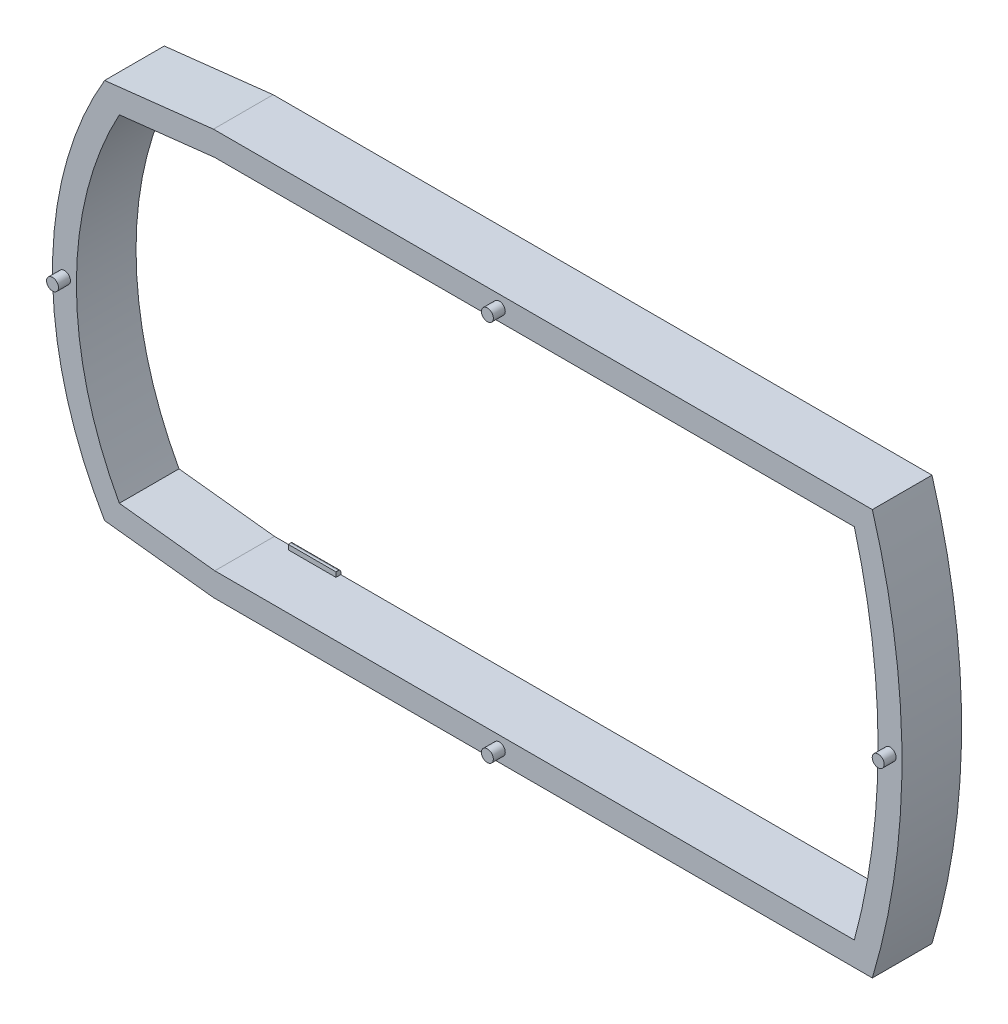
SolidWorks part; units mm, degrees
ref_plane "Plan de face" through (0, 0, 0) normal (0, 0, 1) x (1, 0, 0)
ref_plane "Plan de dessus" through (0, 0, 0) normal (0, 1, 0) x (1, 0, 0)
ref_plane "Plan de droite" through (0, 0, 0) normal (1, 0, 0) x (0, 0, -1)
sketch "Esquisse1" plane through (0, 0, 0) normal (0, 0, 1) x (1, 0, 0)
  line L0 (-192.776, 43.345) -> (-152.776, 47.845)
  line L1 (-152.776, 47.845) -> (115.224, 47.845)
  line L2 (-152.776, 47.845) -> (-152.776, -102.155)
  line L3 (-152.776, -102.155) -> (115.224, -102.155)
  line L4 (115.224, 47.845) -> (115.224, -102.155)
  line L5 (-152.776, 47.845) -> (-192.776, 47.845)
  line L6 (-152.776, 53.8314) -> (-152.776, -102.155)
  line L7 (-152.776, 47.845) -> (-152.776, -102.155)
  line L8 (-152.776, -102.155) -> (-192.776, -102.155)
  line L9 (-192.776, 47.845) -> (-192.776, -102.155)
  line L10 (-152.776, 47.845) -> (-192.776, 47.845)
  line L11 (-152.776, 47.845) -> (-152.776, 43.345)
  line L12 (-152.776, 43.345) -> (-192.776, 43.345)
  line L13 (-192.776, 47.845) -> (-192.776, 43.345)
  line L14 (-152.776, -102.155) -> (-192.776, -102.155)
  line L15 (-152.776, -102.155) -> (-152.776, -97.655)
  line L16 (-152.776, -97.655) -> (-192.776, -97.655)
  line L17 (-192.776, -102.155) -> (-192.776, -97.655)
  line L18 (-192.776, -97.655) -> (-152.776, -102.155)
  line L20 (124.9119, -14.655) -> (121.9119, -14.655)
  line L21 (124.9119, -14.655) -> (124.9119, -39.655)
  line L22 (124.9119, -39.655) -> (121.9119, -39.655)
  line L23 (121.9119, -14.655) -> (121.9119, -39.655)
  line L24 (-144.9874, 47.845) -> (-124.9874, 47.845)
  line L25 (-144.9874, 47.845) -> (-144.9874, 45.845)
  line L26 (-144.9874, 45.845) -> (-124.9874, 45.845)
  line L27 (-124.9874, 47.845) -> (-124.9874, 45.845)
  line L28 (-144.9874, -102.155) -> (-124.9874, -102.155)
  line L29 (-144.9874, -102.155) -> (-144.9874, -100.155)
  line L30 (-144.9874, -100.155) -> (-124.9874, -100.155)
  line L31 (-124.9874, -102.155) -> (-124.9874, -100.155)
  arc A0 (115.224, -102.155) -> (115.224, 47.845) centre (-162.1791, -27.155) ccw
  arc A1 (-192.776, -97.655) -> (-192.776, 43.345) centre (-63.7022, -27.155) cw
  circle A2 centre (-215.776, -27.155) radius 2.5
  circle A3 centre (130.224, -27.155) radius 2.5
  circle A4 centre (-33.549, -107.155) radius 2.5
  circle A5 centre (-33.549, 52.845) radius 2.5
  point P11 (-210.776, -27.155)
  point P12 (125.224, -27.155)
  dimension "D10" = 12.5
  dimension "D19" = 5
  dimension "D1" = 268
  dimension "D2" = 150
  dimension "D3" = 40
  dimension "D4" = 4.5
  dimension "D5" = 4.5
  dimension "D6" = 18
  dimension "D7" = 75
  dimension "D8" = 10
  dimension "D9" = 75
  dimension "D11" = 12.5
  dimension "D12" = 3
  dimension "D13" = 48
  dimension "D14" = 2
  dimension "D15" = 20
  dimension "D16" = 20
  dimension "D17" = 2
  dimension "D18" = 48
  dimension "D21" = 5
  dimension "D22" = 5
  dimension "D23" = 5
extrude "Extru.-Mince1" add sketch "Esquisse1" along normal blind 25 thin contours L3 A0 L1 L0 A1 L18 thin type one direction wall 10
extrude "Boss.-Extru.1" add sketch "Esquisse1<13>" along normal blind 2 separate body contours L20 L23 L22 L21 region at (123.4119, -27.155, 0)
sketch "Esquisse1<13>" plane through (0, 0, 0) normal (0, 0, 1) x (1, 0, 0) same geometry as "Esquisse1"
extrude "Boss.-Extru.2" add sketch "Esquisse1<14>" along normal blind 2 contours L3 L31 L30 L29 region at (-134.9874, -101.155, 0)
sketch "Esquisse1<14>" plane through (0, 0, 0) normal (0, 0, 1) x (1, 0, 0) same geometry as "Esquisse1"
extrude "Boss.-Extru.3" add sketch "Esquisse1<15>" along normal blind 2 contours L27 L1 L25 L26 region at (-134.9874, 46.845, 0)
sketch "Esquisse1<15>" plane through (0, 0, 0) normal (0, 0, 1) x (1, 0, 0) same geometry as "Esquisse1"
fillet "Congé2" radius 1 1 edges at (-134.9874, 45.845, 0)
fillet "Congé3" radius 1 1 edges at (-134.9874, -100.155, 0)
fillet "Congé4" radius 0.5 1 edges at (121.9119, -27.155, 0)
sketch "Esquisse2" plane through (0, 0, 0) normal (0, 1, 0) x (1, 0, 0)
extrude "Boss.-Extru.5" add sketch "Esquisse1<18>" along normal blind 30 contours A4
sketch "Esquisse1<18>" plane through (0, 0, 0) normal (0, 0, 1) x (1, 0, 0) same geometry as "Esquisse1"
extrude "Boss.-Extru.6" add sketch "Esquisse1<19>" along normal blind 30 contours A5
sketch "Esquisse1<19>" plane through (0, 0, 0) normal (0, 0, 1) x (1, 0, 0) same geometry as "Esquisse1"
extrude "Boss.-Extru.7" add sketch "Esquisse1<20>" along normal blind 30 contours A3
sketch "Esquisse1<20>" plane through (0, 0, 0) normal (0, 0, 1) x (1, 0, 0) same geometry as "Esquisse1"
extrude "Boss.-Extru.8" add sketch "Esquisse1<21>" along normal blind 30 contours A2
sketch "Esquisse1<21>" plane through (0, 0, 0) normal (0, 0, 1) x (1, 0, 0) same geometry as "Esquisse1"
